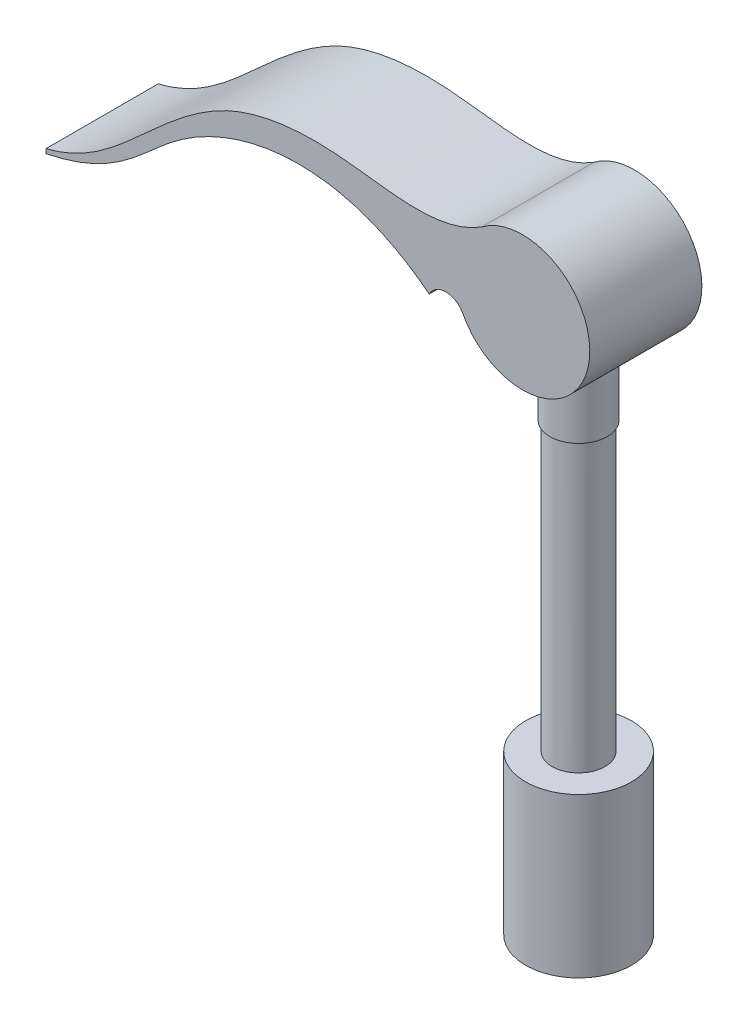
SolidWorks part; units mm, degrees
ref_plane "Front Plane" through (0, 0, 0) normal (0, 0, 1) x (1, 0, 0)
ref_plane "Top Plane" through (0, 0, 0) normal (0, 1, 0) x (1, 0, 0)
ref_plane "Right Plane" through (0, 0, 0) normal (1, 0, 0) x (0, 0, -1)
sketch "Sketch1" plane through (0, 0, 0) normal (0, 1, 0) x (1, 0, 0)
  circle A0 centre (0, 0) radius 3
  dimension "D1" = 6
extrude "Boss-Extrude1" add sketch "Sketch1" along normal mid plane 65
sketch "Sketch2" plane through (0, 0, 0) normal (0, 0, 1) x (1, 0, 0)
  line L0 (-53.975, 20.32) -> (-53.975, 20.828)
  arc A0 (-6.7669, 28.2466) -> (-4.6159, 37.8128) centre (0, 31.75) ccw
  arc A1 (-10.5769, 28.2466) -> (-6.7669, 28.2466) centre (-8.6719, 27.2603) cw
  arc A3 (-4.6159, 37.8128) -> (-6.7669, 28.2466) centre (0, 31.75) ccw construction
  spline S0 degree 3 poles (-53.975, 20.828) (-48.5791, 22.1043) (-42.7392, 28.4513) (-32.7076, 36.2172) (-19.4459, 37.6014) (-9.8051, 34.5284) (-4.6159, 37.8128) knots 0 0 0 0 0.290913 0.47228 0.684924 1 1 1 1
  spline S1 degree 3 poles (-53.975, 20.32) (-46.1217, 21.895) (-37.2728, 34.142) (-20.2627, 35.9482) (-10.5769, 28.2466) knots 0 0 0 0 0.320306 1 1 1 1
  dimension "D1" = 15.24
  dimension "D4" = 11.43
  dimension "D6" = 2.1452
  dimension "D2" = 31.75
  dimension "D3" = 53.975
  dimension "D5" = 3.81
  dimension "D7" = 0.508
  dimension "D8" = 4.6159
extrude "Boss-Extrude2" add sketch "Sketch2" along normal mid plane 12.7
sketch "Sketch3" plane through (0, 0, 0) normal (0, 1, 0) x (1, 0, 0)
  circle A0 centre (0, 0) radius 3.25
  dimension "D1" = 6.5
extrude "Boss-Extrude3" add sketch "Sketch3" along normal up to surface (6.13 mm away) from offset 18 up to face at (0.8715, 31.554, 0)
sketch "Sketch4" plane through (0, -32.5, 0) normal (0, -1, 0) x (1, 0, 0)
  circle A0 centre (0, 0) radius 6
  dimension "D1" = 12
extrude "Boss-Extrude4" add sketch "Sketch4" against normal blind 18
